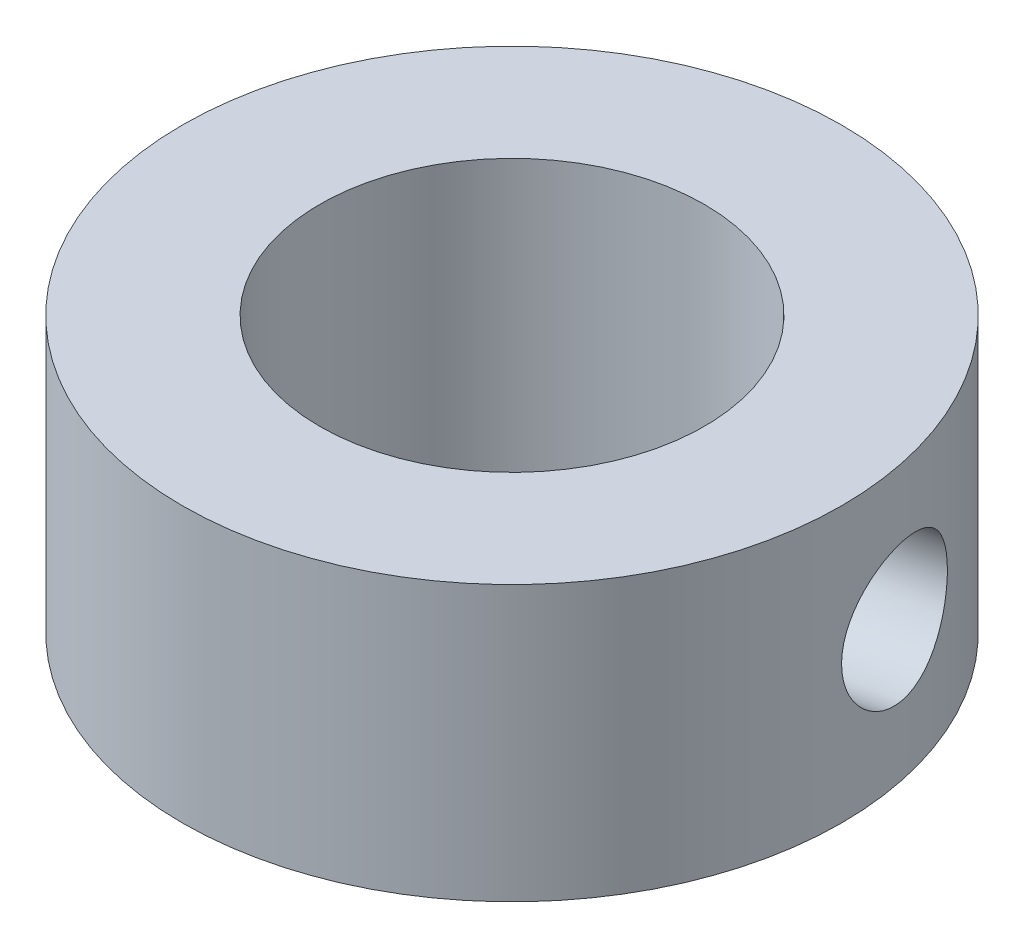
SolidWorks part; units mm, degrees
ref_plane "前视基准面" through (0, 0, 0) normal (0, 0, 1) x (1, 0, 0)
ref_plane "上视基准面" through (0, 0, 0) normal (0, 1, 0) x (1, 0, 0)
ref_plane "右视基准面" through (0, 0, 0) normal (1, 0, 0) x (0, 0, -1)
sketch "草图1" plane through (0, 0, 0) normal (0, 1, 0) x (1, 0, 0)
  circle A0 centre (0, 0) radius 6
  circle A1 centre (0, 0) radius 3.5
  dimension "D1" = 7
  dimension "D2" = 12
extrude "凸台-拉伸1" add sketch "草图1" along normal blind 2.5 and the other way blind 2.5
hole_wizard "M3 螺纹孔2" positions "3D草图4" profile "草图6" tap size "M3" standard "GB" end condition up to next
sketch3d "3D草图4"
  point P0 (5.8689, 0.0058, -1.2476)
sketch "草图6" plane through (5.8689, 0.0058, -1.2476) normal (0, 1, 0) x (-0.2079, 0, -0.9781)
  line L0 (0, 0) -> (0, 2.5)
  line L1 (0, 2.5) -> (1.25, 2.5)
  line L2 (1.25, 2.5) -> (1.25, 0)
  line L5 (1.25, 0) -> (0, 0)
  line L11 (0, -6.35) -> (0, 107.95) construction
  dimension "通孔螺纹孔钻头直径" = 2.5
  dimension "通孔螺纹孔钻头深度" = 2.5
cosmetic thread "孔螺蚊线2" parameters "D2"=3
